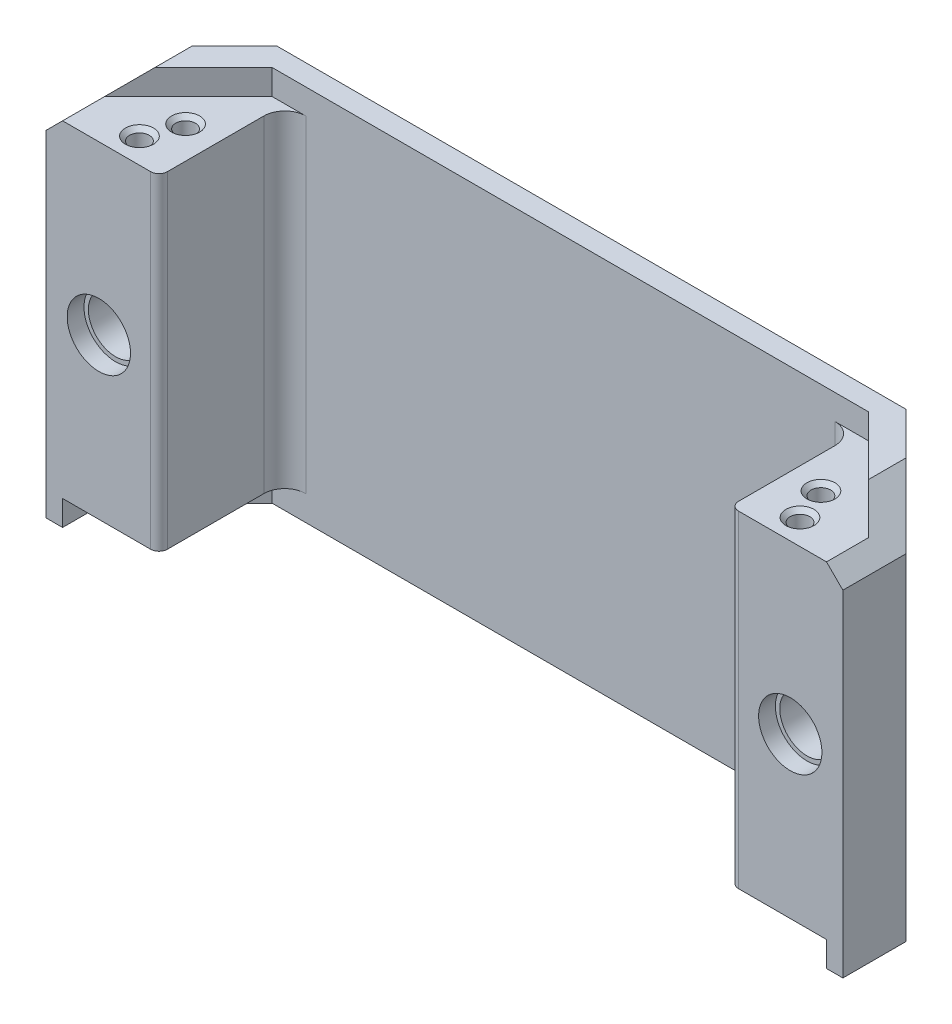
SolidWorks part; units mm, degrees
ref_plane "Front Plane" through (0, 0, 0) normal (0, 0, 1) x (1, 0, 0)
ref_plane "Top Plane" through (0, 0, 0) normal (0, 1, 0) x (1, 0, 0)
ref_plane "Right Plane" through (0, 0, 0) normal (1, 0, 0) x (0, 0, -1)
sketch "Sketch1" plane through (0, 0, 0) normal (0, 0, 1) x (1, 0, 0)
  line L1 (-95, 45) -> (95, 45)
  line L2 (-95, 45) -> (-95, -45)
  line L3 (-95, -45) -> (95, -45)
  line L4 (95, 45) -> (95, -45)
  line L5 (-95, 45) -> (95, -45) construction
  line L6 (-95, -45) -> (95, 45) construction
  point P0 (0, 0)
  point P6 (0, 0)
  dimension "D2" = 190
  dimension "D4" = 90
extrude "Boss-Extrude1" add sketch "Sketch1" along normal blind 5
sketch "Sketch2" plane through (0, 0, 5) normal (0, 0, 1) x (1, 0, 0)
  line L0 (-95, -45) -> (95, -45) construction
  line L1 (-95, 45) -> (-91.1, 45)
  line L2 (-95, 45) -> (-95, -45)
  line L3 (-95, -45) -> (-91.1, -45)
  line L4 (-91.1, 45) -> (-91.1, -45)
  line L5 (0, 0) -> (0, 45) construction
  line L6 (95, 45) -> (-95, 45) construction
  line L7 (95, -45) -> (91.1, -45)
  line L8 (91.1, 45) -> (91.1, -45)
  line L9 (95, 45) -> (91.1, 45)
  line L10 (95, 45) -> (95, -45)
  dimension "D1" = 3.9
extrude "Boss-Extrude2" add sketch "Sketch2" along normal blind 30
sketch "Sketch3" plane through (0, 45, 0) normal (0, 1, 0) x (1, 0, 0)
  line L0 (-91.1, -35) -> (-91.1, -5) construction
  line L1 (-91.1, -14) -> (-57.1, -14)
  line L2 (-91.1, -14) -> (-91.1, -19)
  line L3 (-91.1, -19) -> (-57.1, -19)
  line L4 (-57.1, -14) -> (-57.1, -19)
  line L5 (91.1, -35) -> (91.1, -5) construction
  line L6 (91.1, -14) -> (44.1, -14)
  line L7 (91.1, -14) -> (91.1, -19)
  line L8 (91.1, -19) -> (44.1, -19)
  line L9 (44.1, -14) -> (44.1, -19)
  line L10 (91.1, -5) -> (-91.1, -5) construction
  dimension "D1" = 9
  dimension "D2" = 9
  dimension "D3" = 5
  dimension "D4" = 5
  dimension "D5" = 34
  dimension "D6" = 47
extrude "Boss-Extrude3" add sketch "Sketch3" against normal up to surface (90 mm away) up to face at (0, -45, 18.75)
sketch "Sketch4" plane through (0, 0, 19) normal (0, 0, 1) x (1, 0, 0)
  line L0 (91.1, -45) -> (91.1, 45) construction
  line L1 (-91.1, 45) -> (91.1, 45)
  line L2 (-91.1, 45) -> (-91.1, 39)
  line L3 (-91.1, 39) -> (91.1, 39)
  line L4 (91.1, 45) -> (91.1, 39)
  line L5 (0, 0) -> (-91.1, 0) construction
  line L6 (-91.1, -45) -> (-91.1, 45) construction
  line L7 (-91.1, -39) -> (91.1, -39)
  line L8 (91.1, -45) -> (91.1, -39)
  line L9 (-91.1, -45) -> (91.1, -45)
  line L10 (-91.1, -45) -> (-91.1, -39)
  dimension "D1" = 6
extrude "Cut-Extrude1" cut sketch "Sketch4" against normal blind 5
chamfer "Chamfer6" distance 20 angle 45 4 edges at (91.1, 0, 5) (95, 0, 0) (-95, 0, 0) (-91.1, 0, 5)
sketch "Sketch7" plane through (0, 39, 0) normal (0, 1, 0) x (1, 0, 0)
  line L0 (-85.1, -19) -> (-91.1, -25)
  line L1 (-91.1, -25) -> (-91.1, -35)
  line L2 (-91.1, -35) -> (-68.1, -35)
  line L3 (-68.1, -35) -> (-68.1, -19)
  line L4 (-85.1, -19) -> (-57.1, -19) construction
  line L5 (-68.1, -19) -> (-85.1, -19)
  line L6 (0, 0) -> (0, -5) construction
  line L7 (71.1, -5) -> (-71.1, -5) construction
  line L8 (68.1, -35) -> (68.1, -19)
  line L9 (91.1, -35) -> (68.1, -35)
  line L10 (91.1, -25) -> (91.1, -35)
  line L11 (85.1, -19) -> (91.1, -25)
  line L12 (68.1, -19) -> (85.1, -19)
  dimension "D1" = 23
extrude "Boss-Extrude4" add sketch "Sketch7" against normal up to surface (78 mm away) up to face at (-69.85, -39, 16.5)
fillet "Fillet5" radius 2 2 edges at (-68.1, 0, 35) (68.1, 0, 35)
sketch "Sketch9" plane through (0, 0, 35) normal (0, 0, 1) x (1, 0, 0)
  line L6 (0, 0) -> (0, -45) construction
  line L7 (-71.1, -45) -> (71.1, -45) construction
  line L8 (-95, 45) -> (-95, -45) construction
  line L9 (-95, 39) -> (-82.45, 39) construction
  line L10 (-95, 39) -> (-95, -0.9074) construction
  line L11 (-95, -0.9074) -> (-82.45, -0.9074) construction
  line L12 (-82.45, 39) -> (-82.45, -0.9074) construction
  line L13 (-91.1, 39) -> (-70.1, 39) construction
  circle A0 centre (-82.45, -0.9074) radius 6.5
  circle A1 centre (82.45, -0.9074) radius 6.5
  dimension "D3" = 13
  dimension "D1" = 39.9074
  dimension "D2" = 12.55
extrude "Cut-Extrude4" cut sketch "Sketch9" against normal blind 10
sketch "Sketch10" plane through (0, 0, 35) normal (0, 0, 1) x (1, 0, 0)
  circle A0 centre (-82.45, -0.9074) radius 7.55
  circle A1 centre (82.45, -0.9074) radius 7.55
  dimension "D1" = 15.1
  dimension "D2" = 15.1
extrude "Cut-Extrude5" cut sketch "Sketch10" against normal blind 4
sketch "Sketch15" plane through (0, 39, 0) normal (0, 1, 0) x (1, 0, 0)
  line L0 (68.1, -19) -> (68.1, -33) construction
  line L5 (80.1, -14) -> (44.1, -14) construction
  line L6 (91.1, -35) -> (68.1, -35) construction
  line L7 (91.1, -35) -> (91.1, -14) construction
  line L8 (91.1, -14) -> (68.1, -14) construction
  line L9 (68.1, -35) -> (68.1, -14) construction
  line L10 (68.1, -14) -> (75.7667, -21) construction
  line L11 (75.7667, -21) -> (83.4333, -28) construction
  line L12 (83.4333, -28) -> (91.1, -35) construction
  line L13 (0, 0) -> (0, -5) construction
  line L14 (71.1, -5) -> (-71.1, -5) construction
  line L15 (75.7667, -21) -> (75.7667, -29) construction
  line L16 (75.7667, -29) -> (78.7667, -29) construction
  circle A0 centre (75.7667, -21) radius 2.35
  circle A1 centre (83.4333, -28) radius 2.35 construction
  circle A2 centre (-75.7667, -21) radius 2.35
  circle A3 centre (-83.4333, -28) radius 2.35 construction
  circle A6 centre (78.7667, -29) radius 2.35
  circle A7 centre (-78.7667, -29) radius 2.35
  dimension "D1" = 4.7
  dimension "D2" = 4.7
  dimension "D5" = 4.7
  dimension "D3" = 23
  dimension "D4" = 21
  dimension "D6" = 8
  dimension "D7" = 3
extrude "Cut-Extrude7" cut sketch "Sketch15" against normal blind 8
chamfer "Chamfer7" distance 1 angle 45 4 edges at (-75.7667, 39, 18.65) (75.7667, 39, 23.35) (-78.7667, 39, 26.65) (78.7667, 39, 31.35)
sketch "Sketch17" plane through (0, -39, 0) normal (0, -1, 0) x (1, 0, 0)
  line L0 (0, 0) -> (0, 5) construction
  line L1 (91.1, 35) -> (68.1, 35) construction
  line L2 (91.1, 35) -> (91.1, 19) construction
  line L3 (91.1, 19) -> (68.1, 19) construction
  line L4 (68.1, 35) -> (68.1, 19) construction
  line L5 (-71.1, 5) -> (71.1, 5) construction
  line L6 (68.1, 33) -> (68.1, 19) construction
  line L7 (68.1, 19) -> (44.1, 19) construction
  circle A0 centre (79.6, 27) radius 6.1
  circle A1 centre (-79.6, 27) radius 6.1
  dimension "D2" = 12.2
  dimension "D1" = 11.5
  dimension "D3" = 8
  dimension "D4" = 11.5
extrude "Cut-Extrude8" cut sketch "Sketch17" against normal blind 3.2
fillet "Fillet7" radius 0.2 2 edges at (-85.7, -39, 27) (85.7, -39, 27)
chamfer "Chamfer8" distance 9.9 angle 45 2 edges at (-95, 45, 27.5) (95, 45, 27.5)
sketch "Sketch18" plane through (-57.1, 0, 0) normal (1, 0, 0) x (0, 0, -1)
  line L1 (-19, 39) -> (-14, 39)
  line L2 (-19, 39) -> (-19, -39)
  line L3 (-19, -39) -> (-14, -39)
  line L4 (-14, 39) -> (-14, -39)
extrude "Cut-Extrude9" cut sketch "Sketch18" against normal up to surface and the other way up to surface up to face at (-68.1, 0, 26) other way up to face at (68.1, 0, 26)
sketch "Sketch20" plane through (0, 39, 0) normal (0, 1, 0) x (1, 0, 0)
  line L0 (-68.1, -14) -> (-68.1, -5)
  line L1 (71.1, -5) -> (-71.1, -5) construction
  line L2 (-68.1, -5) -> (-71.1, -5)
  line L3 (-71.1, -5) -> (-80.1, -14)
  line L4 (-80.1, -14) -> (-68.1, -14)
  line L5 (0, 0) -> (0, -5) construction
  line L6 (71.1, -5) -> (80.1, -14)
  line L7 (68.1, -5) -> (71.1, -5)
  line L8 (68.1, -14) -> (68.1, -5)
  line L9 (80.1, -14) -> (68.1, -14)
extrude "Boss-Extrude5" add sketch "Sketch20" against normal up to surface (78 mm away) up to face at (-85.9, -39, 27)
fillet "Fillet8" radius 5 2 edges at (68.1, 0, 5) (-68.1, 0, 5)
